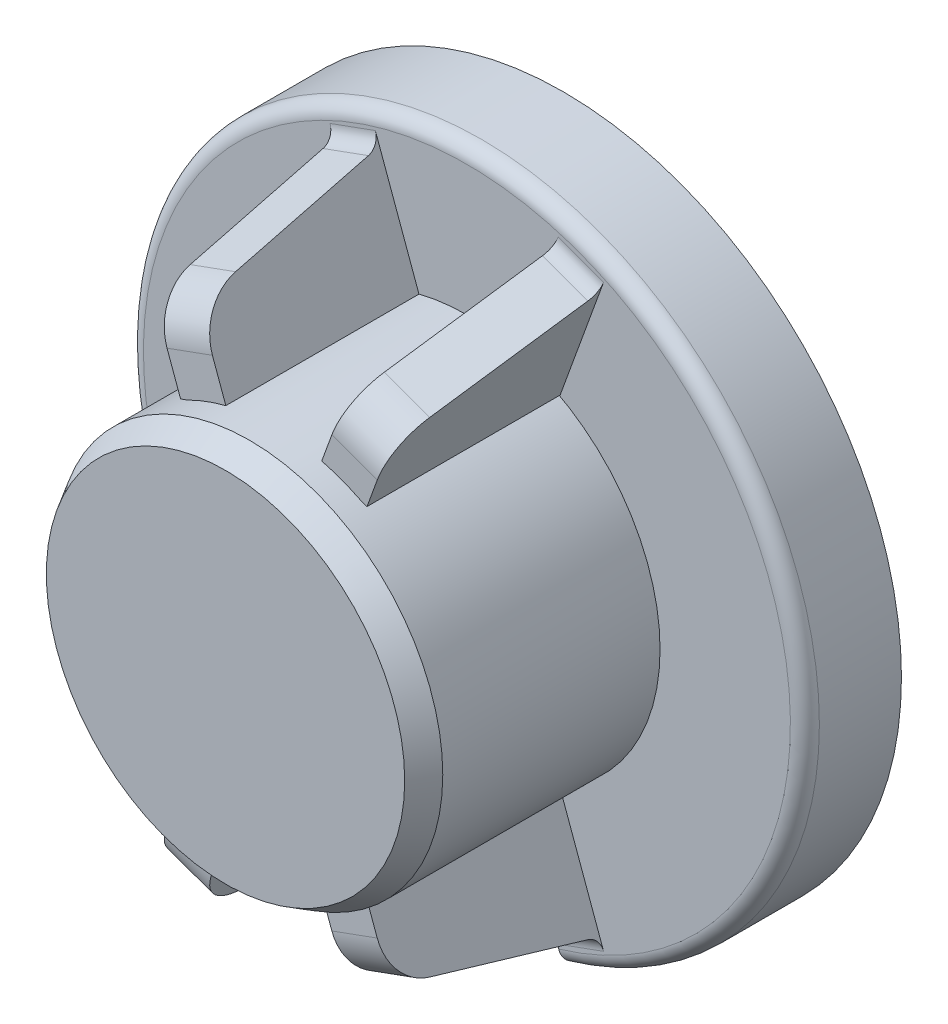
SolidWorks part; units mm, degrees
ref_plane "Płaszczyzna przednia" through (0, 0, 0) normal (0, 0, 1) x (1, 0, 0)
ref_plane "Płaszczyzna górna" through (0, 0, 0) normal (0, 1, 0) x (1, 0, 0)
ref_plane "Płaszczyzna prawa" through (0, 0, 0) normal (1, 0, 0) x (0, 0, -1)
sketch "Szkic1" plane through (0, 0, 0) normal (0, 0, 1) x (1, 0, 0)
  line L0 (1.5, -2.5981) -> (1.5, 2.5981)
  circle A0 centre (0, 0) radius 3
  circle A1 centre (0, 0) radius 4
  circle A2 centre (0, 0) radius 7
  point P5 (-3, 0)
  dimension "D1" = 6
  dimension "D3" = 8
  dimension "D4" = 14
  dimension "D2" = 4.5
extrude "Dodanie-wyciągnięcie1" add sketch "Szkic1" along normal blind 6 contours A1 A0 | L0 A0 region at (2.1151, 0, 0) region at (-3.8869, 0, 0)
extrude "Dodanie-wyciągnięcie2" add sketch "Szkic1<3>" along normal blind 2 contours A2 A1 region at (-6.802, 0, 0)
sketch "Szkic1<3>" plane through (0, 0, 0) normal (0, 0, 1) x (1, 0, 0) same geometry as "Szkic1"
extrude "Dodanie-wyciągnięcie3" add sketch "Szkic1<4>" along normal blind 1 from offset 6 contours L0 A0 | L0 A0 | A1 A0 region at (-0.514, 0, 0) region at (2.1151, 0, 0) region at (-3.8869, 0, 0)
sketch "Szkic1<4>" plane through (0, 0, 0) normal (0, 0, 1) x (1, 0, 0) same geometry as "Szkic1"
chamfer "Sfazowanie1" distance 0.5 angle 30 2 edges at (-3, 0, 6) (1.5, 0, 6) first distance on face at (-0.75, 0, 6)
chamfer "Sfazowanie2" distance 0.5 angle 30 1 edges at (4, 0, 7) first distance on face at (4, 0, 2)
sketch "Szkic3" plane through (0, 0, 2) normal (0, 0, 1) x (1, 0, 0)
  line L0 (0, -4) -> (0, -7)
  line L1 (1.4606, -3.697) -> (2.2815, -5.9523)
  line L2 (-1.4606, -3.697) -> (-2.2815, -5.9523)
  circle A0 centre (0, 0) radius 4 construction
  circle A1 centre (0, 0) radius 7 construction
  dimension "D1" = 20
  dimension "D2" = 2.4
extrude "Wyciągnięcie-cienka ścianka1" add sketch "Szkic3" along normal blind 4 thin contours L1 | L2 thin type mid plane wall 1
sketch "Szkic4" plane through (-0.5714, 0.208, 0) normal (-0.9397, 0.342, 0) x (0, 0, 1)
  line L4 (6, -6.3736) -> (6, -5.6236)
  line L5 (6, -3.9736) -> (6, -6.3736) construction
  line L6 (2, -6.3736) -> (6, -6.3736)
  line L7 (2, -6.3736) -> (6, -5.6236)
  dimension "D1" = 0.75
extrude "Wytnij-wyciągnięcie1" cut sketch "Szkic4" against normal blind 4
sketch "Szkic5" plane through (-0.3683, -0.134, 0) normal (-0.9397, -0.342, 0) x (0, 0, 1)
  line L0 (2, -6.3736) -> (6, -6.3736)
  line L1 (6, -6.3736) -> (6, -5.3736)
  line L2 (6, -3.9808) -> (6, -6.3736) construction
  line L3 (6, -5.3736) -> (2, -6.3736)
  dimension "D1" = 1
extrude "Wytnij-wyciągnięcie2" cut sketch "Szkic5" against normal blind 4
fillet "Zaokrąglenie2" radius 1 2 edges at (1.9394, -5.0126, 6) (-2.0249, -5.2475, 6)
sketch "Szkic6" plane through (0, 0, 2) normal (0, 0, 1) x (1, 0, 0)
  line L2 (-1.8116, -6.1233) -> (-2.0221, -6.7016)
  line L3 (0.9932, -3.8747) -> (1.8116, -6.1233)
  line L4 (1.8116, -6.1233) -> (1.9859, -6.7124)
  line L5 (-0.9932, -3.8747) -> (-1.8116, -6.1233)
  arc A0 (1.9859, -6.7124) -> (-2.0221, -6.7016) centre (0, 0) cw
  circle A3 centre (0, 0) radius 7 construction
  arc A4 (0.9932, -3.8747) -> (-0.9932, -3.8747) centre (0, 0) cw
extrude "Wytnij-wyciągnięcie3" cut sketch "Szkic6" against normal blind 4
fillet "Zaokrąglenie4" radius 0.3 2 edges at (2.2815, -5.9523, 2) (-2.2815, -5.9523, 2)
fillet "Zaokrąglenie5" radius 0.3 1 edges at (0.0189, 7, 2)
mirror "Lustro2" about plane through (0, 0, 0) normal (0, 1, 0) of "Wytnij-wyciągnięcie2", "Zaokrąglenie2", "Wytnij-wyciągnięcie1", "Wyciągnięcie-cienka ścianka1", "Zaokrąglenie4"
